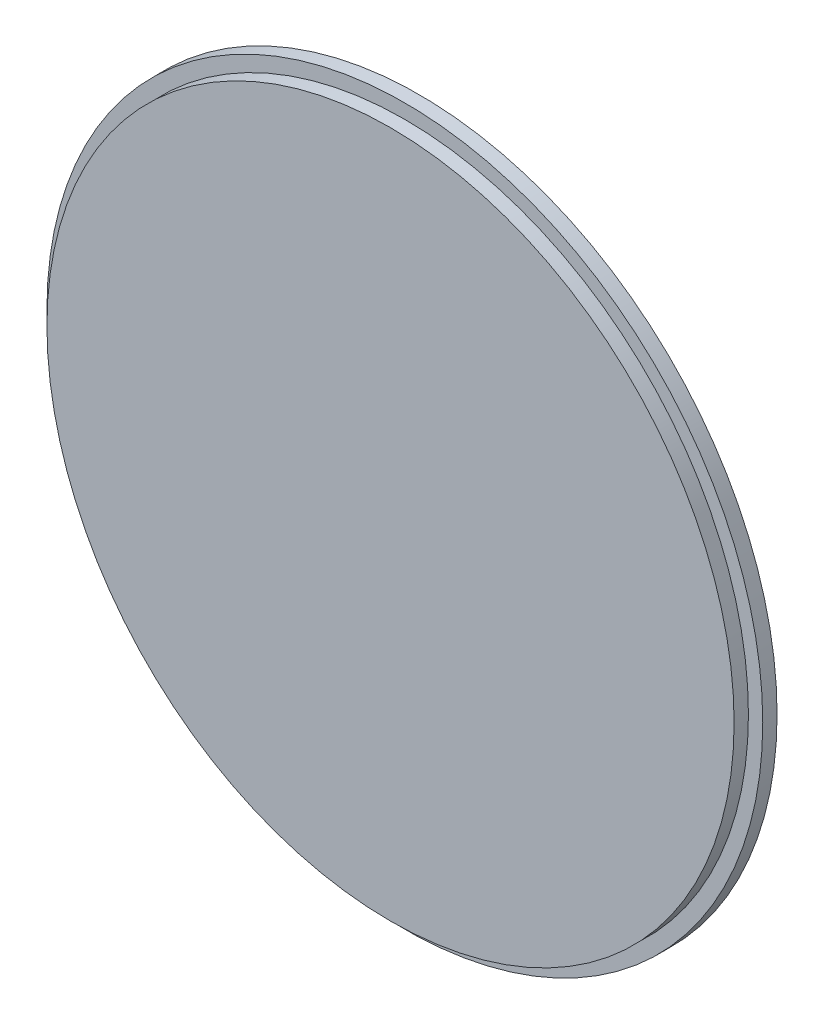
SolidWorks part; units mm, degrees
ref_plane "Front Plane" through (0, 0, 0) normal (0, 0, 1) x (1, 0, 0)
ref_plane "Top Plane" through (0, 0, 0) normal (0, 1, 0) x (1, 0, 0)
ref_plane "Right Plane" through (0, 0, 0) normal (1, 0, 0) x (0, 0, -1)
sketch "Sketch1" plane through (0, 0, 0) normal (0, 0, 1) x (1, 0, 0)
  circle A0 centre (0, 0) radius 79.375
  dimension "D1" = 158.75
extrude "Boss-Extrude1" add sketch "Sketch1" along normal blind 3.175
sketch "Sketch2" plane through (0, 0, 3.175) normal (0, 0, 1) x (1, 0, 0)
  circle A0 centre (0, 0) radius 76.2
  dimension "D1" = 152.4
extrude "Boss-Extrude2" add sketch "Sketch2" along normal blind 3.175
